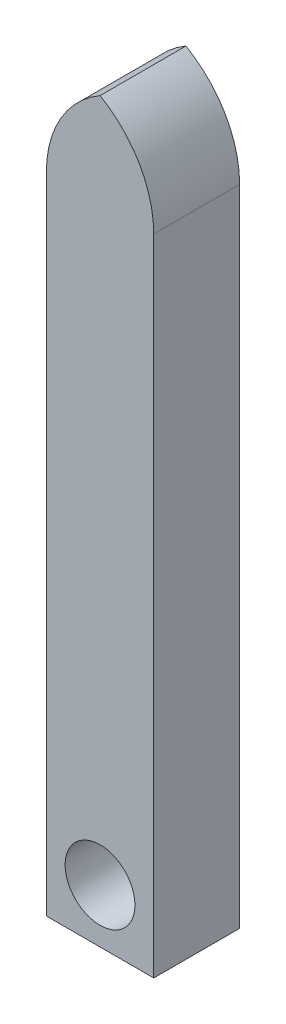
SolidWorks part; units mm, degrees
ref_plane "Front Plane" through (0, 0, 0) normal (0, 0, 1) x (1, 0, 0)
ref_plane "Top Plane" through (0, 0, 0) normal (0, 1, 0) x (1, 0, 0)
ref_plane "Right Plane" through (0, 0, 0) normal (1, 0, 0) x (0, 0, -1)
sketch "Sketch1" plane through (0, 0, 0) normal (0, 0, 1) x (1, 0, 0)
  line L0 (0, -17.5) -> (0, -15) construction
  line L1 (-2.5, -17.5) -> (2.5, -17.5)
  line L2 (-2.5, -17.5) -> (-2.5, 17.5)
  line L3 (-2.5, 17.5) -> (2.5, 17.5)
  line L4 (2.5, -17.5) -> (2.5, 17.5)
  line L5 (-2.5, -17.5) -> (2.5, 17.5) construction
  line L6 (-2.5, 17.5) -> (2.5, -17.5) construction
  circle A0 centre (0, -15) radius 1.625
  point P0 (0, 0)
  dimension "D3" = 3.25
  dimension "D1" = 5
  dimension "D2" = 35
  dimension "D4" = 2.5
extrude "Boss-Extrude1" add sketch "Sketch1" along normal blind 4
fillet "Fillet1" radius 5 2 edges at (-2.5, 17.5, 2) (2.5, 17.5, 2)
equation "\"D4@Sketch1\"=\"D1@Sketch1\"/2"
